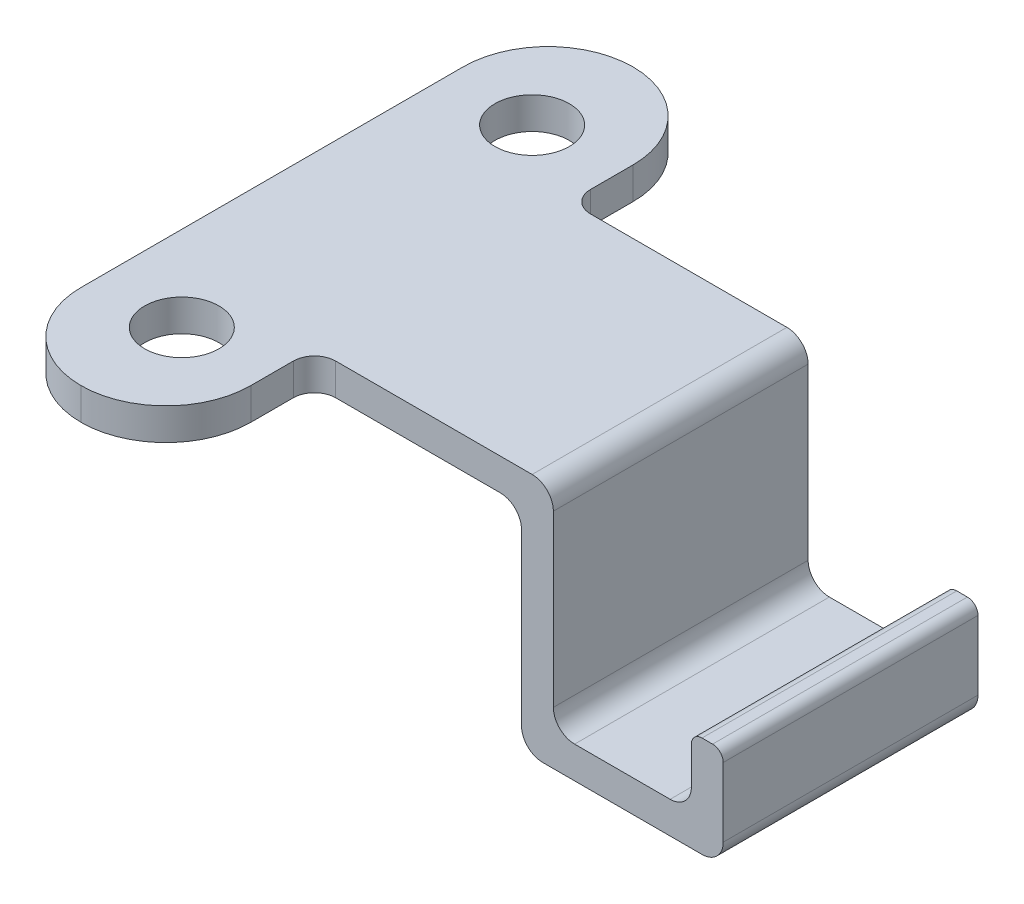
SolidWorks part; units mm, degrees
material "AISI 304"
ref_plane "前视基准面" through (0, 0, 0) normal (0, 0, 1) x (1, 0, 0)
ref_plane "上视基准面" through (0, 0, 0) normal (0, 1, 0) x (1, 0, 0)
ref_plane "右视基准面" through (0, 0, 0) normal (1, 0, 0) x (0, 0, -1)
sketch "草图1" plane through (0, 0, 0) normal (0, 0, 1) x (1, 0, 0)
  line L0 (0, 0) -> (18.5, 0) construction
  line L1 (18.5, 0) -> (18.5, -10) construction
  line L2 (18.5, -10) -> (26.5, -10) construction
  line L3 (26.5, -10) -> (26.5, -6) construction
  line L4 (0, -0.75) -> (17.75, -0.75)
  line L5 (17.75, -0.75) -> (17.75, -10.75)
  line L6 (17.75, -10.75) -> (27.25, -10.75)
  line L7 (27.25, -10.75) -> (27.25, -6)
  line L8 (0, 0.75) -> (19.25, 0.75)
  line L9 (19.25, 0.75) -> (19.25, -9.25)
  line L10 (19.25, -9.25) -> (25.75, -9.25)
  line L11 (25.75, -9.25) -> (25.75, -6)
  line L12 (0, -0.75) -> (0, 0.75)
  line L13 (25.75, -6) -> (27.25, -6)
  dimension "D1" = 18.5
  dimension "D2" = 10
  dimension "D3" = 8
  dimension "D4" = 4
  dimension "D5" = 0.75
  dimension "D6" = 0.75
extrude "凸台-拉伸1" add sketch "草图1" along normal mid plane 26
sketch "草图2" plane through (0, 0.75, 0) normal (0, 1, 0) x (1, 0, 0)
  line L0 (19.25, 13) -> (0, 13) construction
  line L1 (8, 13) -> (27.25, 13)
  line L2 (8, 13) -> (8, 6)
  line L3 (8, 6) -> (27.25, 6)
  line L4 (27.25, 13) -> (27.25, 6)
  line L5 (27.25, -13) -> (27.25, 13) construction
  line L6 (19.25, -13) -> (0, -13) construction
  line L7 (8, -13) -> (27.25, -13)
  line L8 (8, -13) -> (8, -6)
  line L9 (8, -6) -> (27.25, -6)
  line L10 (27.25, -13) -> (27.25, -6)
  line L11 (0, 0) -> (-50000, 0) construction
  line L12 (0, -13) -> (0, 13) construction
  point P18 (0, 0)
  dimension "D1" = 12
  dimension "D2" = 8
extrude "切除-拉伸1" cut sketch "草图2" against normal blind 16
sketch "草图3" plane through (0, 0.75, 0) normal (0, 1, 0) x (1, 0, 0)
  line L0 (4, 8.25) -> (4, -8.25) construction
  line L1 (0, 0) -> (50000, 0) construction
  line L2 (0, -13) -> (0, 13) construction
  line L4 (8, 13) -> (8, 6) construction
  circle A0 centre (4, 8.25) radius 1.75
  circle A1 centre (4, -8.25) radius 1.75
  point P8 (0, 0)
  dimension "D1" = 3.5
  dimension "D3" = 4
  dimension "D2" = 16.5
extrude "切除-拉伸2" cut sketch "草图3" against normal blind 6
fillet "圆角1" radius 4 4 edges at (8, 0, 13) (0, 0, 13) (0, 0, -13) (8, 0, -13)
fillet "圆角2" radius 1 2 edges at (8, 0, -6) (8, 0, 6)
fillet "圆角3" radius 1 6 edges at (25.75, -9.25, 0) (19.25, -9.25, 0) (27.25, -10.75, 0) (17.75, -10.75, 0) (17.75, -0.75, 0) (19.25, 0.75, 0)
fillet "圆角4" radius 0.5 2 edges at (25.75, -6, 0) (27.25, -6, 0)
